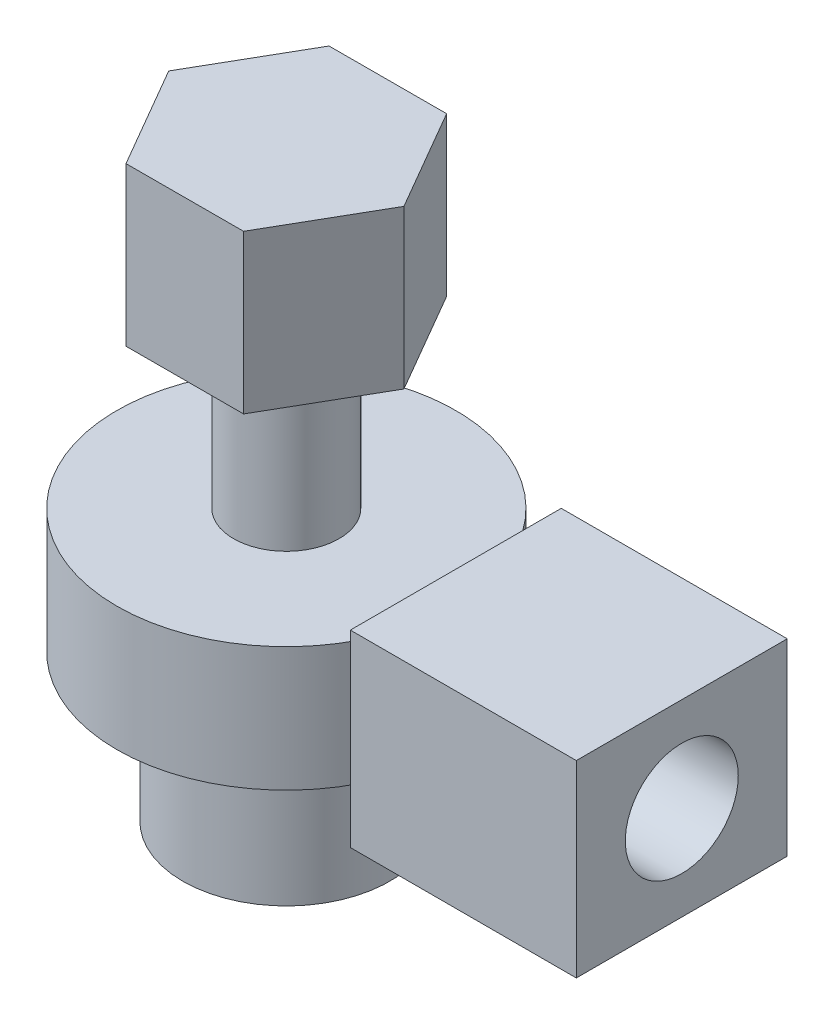
SolidWorks part; units mm, degrees
ref_plane "Front Plane" through (0, 0, 0) normal (0, 0, 1) x (1, 0, 0)
ref_plane "Top Plane" through (0, 0, 0) normal (0, 1, 0) x (1, 0, 0)
ref_plane "Right Plane" through (0, 0, 0) normal (1, 0, 0) x (0, 0, -1)
sketch "Sketch1" plane through (0, 0, 0) normal (0, 1, 0) x (1, 0, 0)
  circle A0 centre (0, 0) radius 2.75
  dimension "D1" = 5.5
extrude "Boss-Extrude1" add sketch "Sketch1" along normal blind 3.2
sketch "Sketch2" plane through (0, 3.2, 0) normal (0, 1, 0) x (1, 0, 0)
  circle A0 centre (0, 0) radius 1.4
  dimension "D1" = 2.8
extrude "Boss-Extrude2" add sketch "Sketch2" along normal blind 8.3
sketch "Sketch3" plane through (0, 11.5, 0) normal (0, 1, 0) x (1, 0, 0)
  line L1 (1.5546, 2.7024) -> (-1.563, 2.6976)
  line L2 (-1.563, 2.6976) -> (-3.1177, -0.0048)
  line L3 (-3.1177, -0.0048) -> (-1.5546, -2.7024)
  line L4 (-1.5546, -2.7024) -> (1.563, -2.6976)
  line L5 (1.563, -2.6976) -> (3.1177, 0.0048)
  line L6 (3.1177, 0.0048) -> (1.5546, 2.7024)
  circle A0 centre (0, 0) radius 2.7 construction
  dimension "D1" = 5.4
extrude "Boss-Extrude3" add sketch "Sketch3" along normal blind 4.2
ref_plane "Plane1" through (0, 3.9, 0) normal (0, 1, 0) x (1, 0, 0)
sketch "Sketch6" plane through (0, 3.9, 0) normal (0, 1, 0) x (1, 0, 0)
  circle A0 centre (0, 0) radius 4.5
  dimension "D1" = 9
extrude "Boss-Extrude5" add sketch "Sketch6" along normal blind 3.3
ref_plane "Plane2" through (4.5, 0, 0) normal (1, 0, 0) x (0, 0, -1)
sketch "Sketch7" plane through (4.5, 0, 0) normal (1, 0, 0) x (0, 0, -1)
  line L1 (-2.8, 3.05) -> (2.8, 3.05)
  line L2 (-2.8, 3.05) -> (-2.8, 8.05)
  line L3 (-2.8, 8.05) -> (2.8, 8.05)
  line L4 (2.8, 3.05) -> (2.8, 8.05)
  line L5 (-2.8, 3.05) -> (2.8, 8.05) construction
  line L6 (-2.8, 8.05) -> (2.8, 3.05) construction
  point P0 (0, 5.55)
  point P5 (0, 3.05)
  dimension "D1" = 5
  dimension "D2" = 5.6
  dimension "D3" = 5.55
extrude "Boss-Extrude6" add sketch "Sketch7" along normal blind 6 separate body
sketch "Sketch8" plane through (10.5, 0, 0) normal (1, 0, 0) x (0, 0, -1)
  line L3 (2.8, 3.05) -> (2.8, 8.05) construction
  line L4 (2.8, 8.05) -> (-2.8, 8.05) construction
  circle A0 centre (0, 5.55) radius 1.5
  point P6 (2.8, 5.55)
  point P7 (0, 8.05)
  dimension "D1" = 3
extrude "Cut-Extrude1" cut sketch "Sketch8" against normal blind 5
